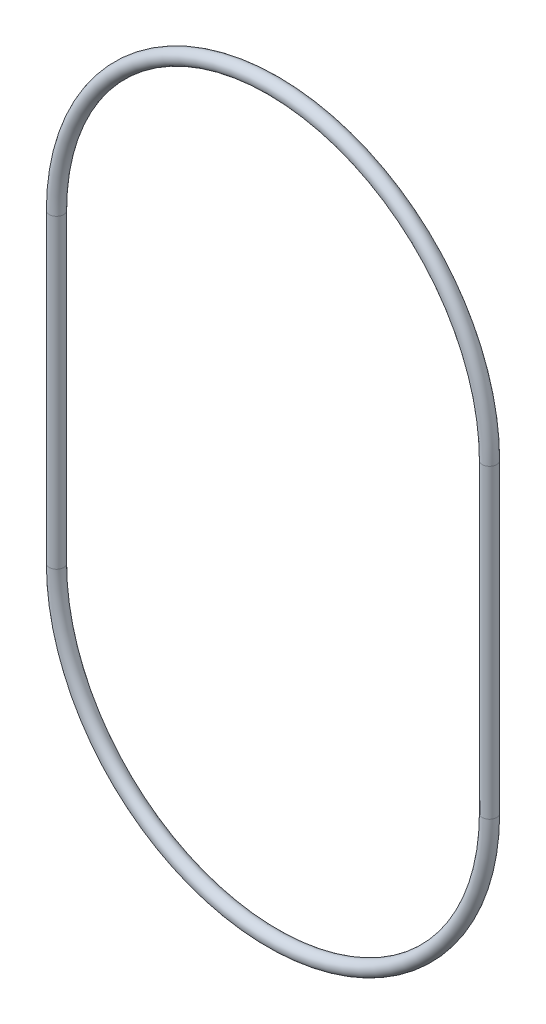
SolidWorks part; units mm, degrees
ref_plane "Plan1" through (0, 0, 0) normal (0, 0, 1) x (1, 0, 0)
ref_plane "Plan2" through (0, 0, 0) normal (0, 1, 0) x (1, 0, 0)
ref_plane "Plan3" through (0, 0, 0) normal (1, 0, 0) x (0, 0, -1)
ref_axis "Axe3" through (0, -50, 0) along (0, 1, 0)
ref_axis "Axe4" through (-50, 0, 0) along (1, 0, 0)
sketch "Esquisse1" plane through (0, 0, 0) normal (0, 0, 1) x (1, 0, 0)
  line L0 (-34, 0) -> (-34, -48)
  line L1 (34, 0) -> (34, -48)
  arc A0 (34, 0) -> (-34, 0) centre (0, 0) ccw
  arc A1 (-34, -48) -> (34, -48) centre (0, -48) ccw
  dimension "D1" = 68
  dimension "D2" = 68
  dimension "D3" = 48
sketch "Esquisse2" plane through (0, 0, 0) normal (0, 1, 0) x (1, 0, 0)
  circle A0 centre (34, 0) radius 1.125
  dimension "D2" = 2.25
  dimension "D1" = 34
sweep "Base-Balayage" add profiles "Esquisse2" path "Esquisse1"
